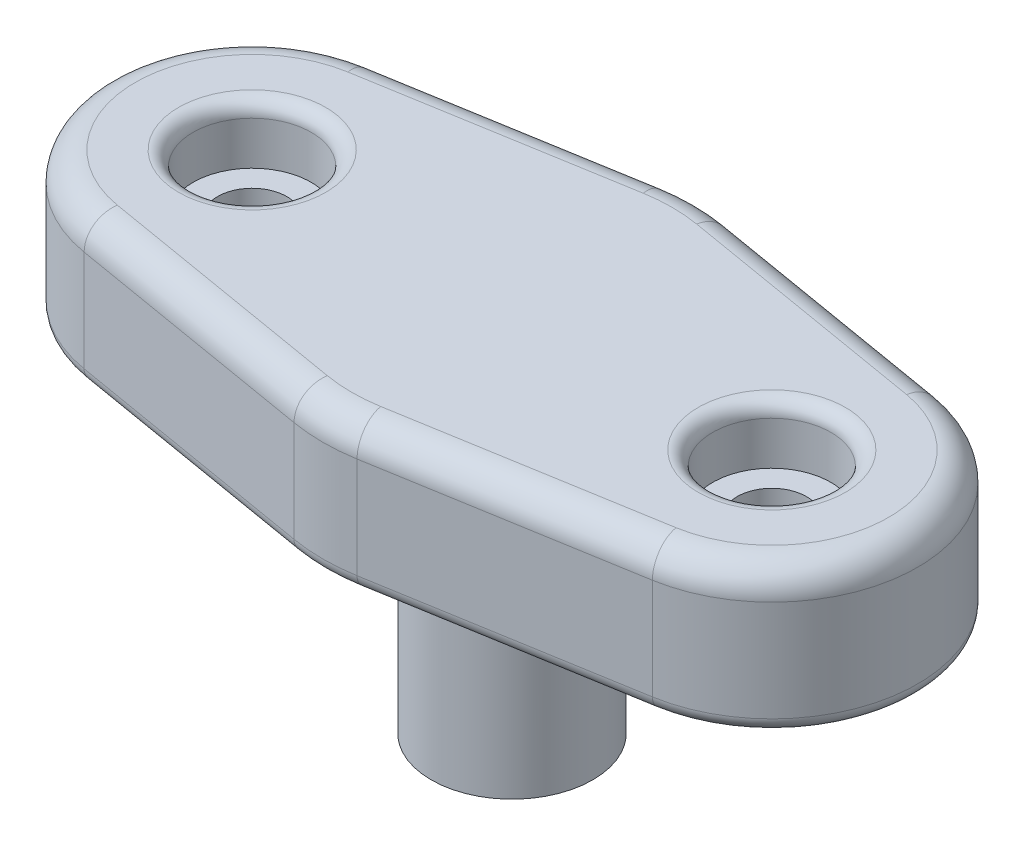
SolidWorks part; units mm, degrees
ref_plane "Front Plane" through (0, 0, 0) normal (0, 0, 1) x (1, 0, 0)
ref_plane "Top Plane" through (0, 0, 0) normal (0, 1, 0) x (1, 0, 0)
ref_plane "Right Plane" through (0, 0, 0) normal (1, 0, 0) x (0, 0, -1)
sketch "Sketch1" plane through (0, 0, 0) normal (0, 1, 0) x (1, 0, 0)
  circle A0 centre (0, 0) radius 2.8
  dimension "D1" = 5.6
extrude "Boss-Extrude1" add sketch "Sketch1" along normal blind 8
sketch "Sketch2" plane through (0, 8, 0) normal (0, 1, 0) x (1, 0, 0)
  line L0 (-9, 0) -> (9, 0) construction
  line L1 (-9.8417, 4.9794) -> (-1.0917, 6.4584)
  line L4 (9.8417, -4.9794) -> (1.0917, -6.4584)
  line L5 (1.0917, 6.4584) -> (9.8417, 4.9794)
  line L6 (-1.0917, -6.4584) -> (-9.8417, -4.9794)
  circle A0 centre (-9, 0) radius 1.2
  circle A1 centre (9, 0) radius 1.2
  arc A2 (-9.8417, 4.9794) -> (-9.8417, -4.9794) centre (-9, 0) ccw
  arc A3 (9.8417, -4.9794) -> (9.8417, 4.9794) centre (9, 0) ccw
  arc A4 (-1.0917, -6.4584) -> (1.0917, -6.4584) centre (0, 0) ccw
  arc A5 (1.0917, 6.4584) -> (-1.0917, 6.4584) centre (0, 0) ccw
  point P4 (0, 0)
  dimension "D1" = 2.4
  dimension "D2" = 2.4
  dimension "D4" = 10.1
  dimension "D5" = 10.1
  dimension "D6" = 13.1
  dimension "D3" = 18
extrude "Boss-Extrude2" add sketch "Sketch2" along normal blind 5
sketch "Sketch3" plane through (0, 13, 0) normal (0, 1, 0) x (1, 0, 0)
  circle A0 centre (-9, 0) radius 2.05
  circle A1 centre (9, 0) radius 2.05
  dimension "D1" = 4.1
  dimension "D2" = 4.1
extrude "Cut-Extrude1" cut sketch "Sketch3" against normal blind 2
fillet "Fillet1" radius 0.5 10 edges at (-14.05, 8, 0) (-5.4667, 8, -5.7189) (0, 8, -6.55) (5.4667, 8, -5.7189) (14.05, 8, 0) (5.4667, 8, 5.7189) (0, 8, 6.55) (-5.4667, 8, 5.7189) (9, 13, 2.05) (-9, 13, 2.05)
fillet "Fillet2" radius 1 8 edges at (-5.4667, 13, -5.7189) (0, 13, -6.55) (5.4667, 13, -5.7189) (14.05, 13, 0) (5.4667, 13, 5.7189) (0, 13, 6.55) (-5.4667, 13, 5.7189) (-14.05, 13, 0)
sketch "Sketch5" plane through (0, 0, 0) normal (0, -1, 0) x (1, 0, 0)
  circle A0 centre (0, 0) radius 2
  dimension "D1" = 4
extrude "Cut-Extrude2" cut sketch "Sketch5" against normal blind 2
fillet "Fillet3" radius 1 2 edges at (0, 2, -2) (0, 0, -2)
